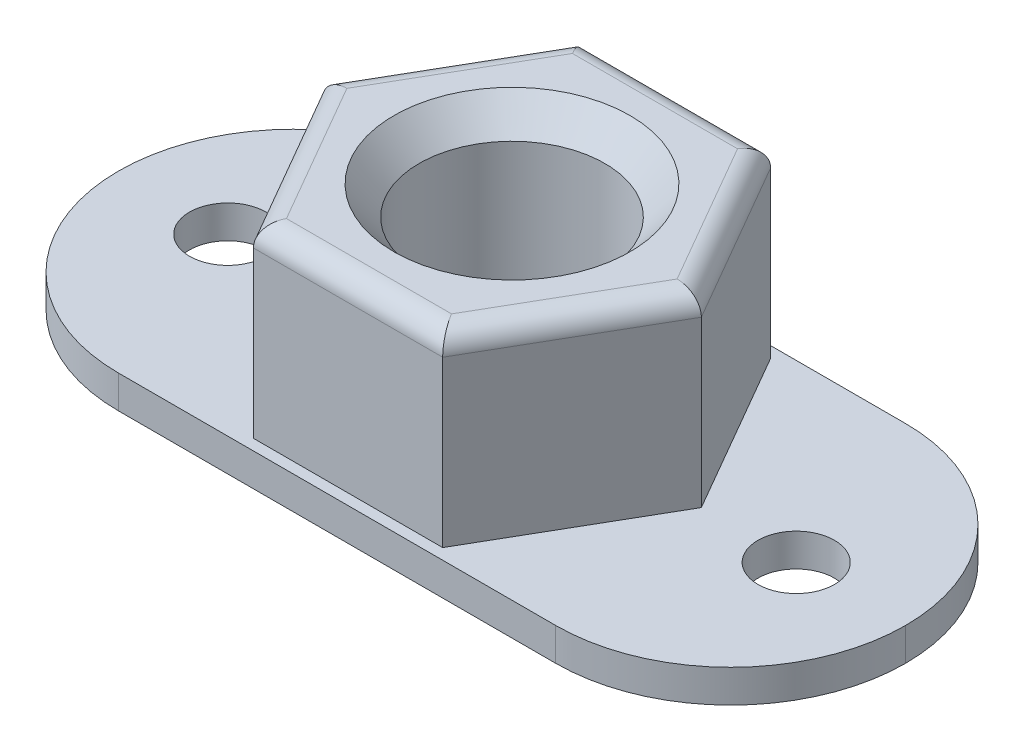
SolidWorks part; units mm, degrees
material "Plain Carbon Steel"
ref_plane "Front Plane" through (0, 0, 0) normal (0, 0, 1) x (1, 0, 0)
ref_plane "Top Plane" through (0, 0, 0) normal (0, 1, 0) x (1, 0, 0)
ref_plane "Right Plane" through (0, 0, 0) normal (1, 0, 0) x (0, 0, -1)
sketch "Sketch1" plane through (0, 0, 0) normal (0, 1, 0) x (1, 0, 0)
  line L1 (13.7482, 0) -> (6.8741, 11.9063)
  line L2 (6.8741, 11.9063) -> (-6.8741, 11.9063)
  line L3 (-6.8741, 11.9063) -> (-13.7482, 0)
  line L4 (-13.7482, 0) -> (-6.8741, -11.9062)
  line L5 (-6.8741, -11.9062) -> (6.8741, -11.9062)
  line L6 (6.8741, -11.9062) -> (13.7482, 0)
  circle A0 centre (0, 0) radius 11.9062 construction
  dimension "D1" = 23.8125
extrude "Boss-Extrude1" add sketch "Sketch1" along normal blind 13.4937
hole_wizard "5/8-11 Tapped Hole1" positions "Sketch2" profile "Sketch3" tap size "5/8-11" standard "ANSI Inch" end condition through all
sketch "Sketch2" plane through (0, 13.4937, 0) normal (0, 1, 0) x (1, 0, 0)
  point P0 (0, 0)
sketch "Sketch3" plane through (0, 13.4937, 0) normal (1, 0, 0) x (0, 0, 1)
  line L0 (0, 0) -> (0, 13.4937)
  line L1 (0, 13.4937) -> (6.7462, 13.4937)
  line L2 (6.7462, 13.4937) -> (6.7462, 2.1009)
  line L3 (6.7462, 2.1009) -> (8.5725, 0)
  line L5 (8.5725, 0) -> (0, 0)
  line L6 (-6.7462, 2.1009) -> (-8.5725, 0) construction
  line L11 (0, -6.35) -> (0, 107.95) construction
  dimension "Thru Tap Drill Dia." = 13.4925
  dimension "Thru Tap Drill Depth" = 13.4937
  dimension "Near C'Sink Dia." = 17.145
  dimension "Near C'Sink Angle" = 82
cosmetic thread "Hole Thread1" parameters "D1"=13.4937, "D2"=15.875
fillet "Fillet1" radius 1.524 6 edges at (0, 13.4937, -11.9063) (10.3111, 13.4937, -5.9531) (10.3111, 13.4937, 5.9531) (0, 13.4937, 11.9062) (-10.3111, 13.4937, 5.9531) (-10.3111, 13.4937, -5.9531)
sketch "Sketch4" plane through (0, 0, 0) normal (0, -1, 0) x (1, 0, 0)
  line L1 (-28.575, -12.7) -> (28.575, -12.7)
  line L2 (-28.575, -12.7) -> (-28.575, 12.7)
  line L3 (-28.575, 12.7) -> (28.575, 12.7)
  line L4 (28.575, -12.7) -> (28.575, 12.7)
  line L5 (-28.575, -12.7) -> (28.575, 12.7) construction
  line L6 (-28.575, 12.7) -> (28.575, -12.7) construction
  point P0 (0, 0)
  dimension "D1" = 25.4
  dimension "D2" = 57.15
extrude "Boss-Extrude2" add sketch "Sketch4" along normal blind 2.3813
fillet "Fillet2" radius 12.7 4 edges at (-28.575, -1.1906, -12.7) (-28.575, -1.1906, 12.7) (28.575, -1.1906, -12.7) (28.575, -1.1906, 12.7)
sketch "Sketch5" plane through (0, -2.3813, 0) normal (0, -1, 0) x (1, 0, 0)
  circle A0 centre (0, 0) radius 9.525
  dimension "D1" = 19.05
extrude "Cut-Extrude1" cut sketch "Sketch5" against normal up to surface (2.3813 mm away) up to face at (0, 0, 0)
sketch "Sketch6" plane through (0, -2.3813, 0) normal (0, -1, 0) x (1, 0, 0)
  circle A0 centre (-20.6375, 0) radius 2.7781
  circle A1 centre (20.6375, 0) radius 2.7781
  dimension "D1" = 5.5562
  dimension "D2" = 5.5562
  dimension "D3" = 20.6375
  dimension "D4" = 41.275
extrude "Cut-Extrude2" cut sketch "Sketch6" against normal through all
